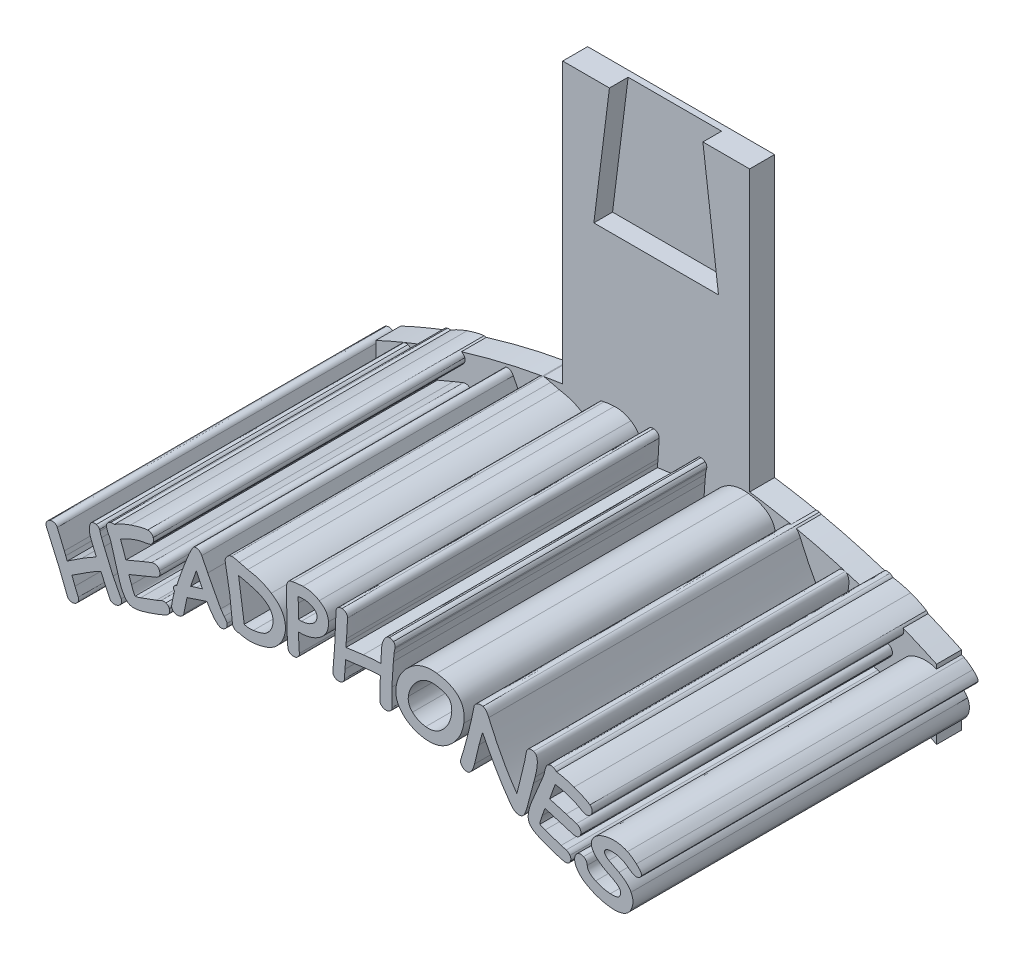
SolidWorks part; units mm, degrees
ref_plane "Front Plane" through (0, 0, 0) normal (0, 0, 1) x (1, 0, 0)
ref_plane "Top Plane" through (0, 0, 0) normal (0, 1, 0) x (1, 0, 0)
ref_plane "Right Plane" through (0, 0, 0) normal (1, 0, 0) x (0, 0, -1)
sketch "Sketch1" plane through (0, 0, 0) normal (0, 0, 1) x (1, 0, 0)
  line L1 (45, 21.1673) -> (-7.9986, 21.1673) construction
  line L2 (0, 0) -> (0, 11.1673)
  line L3 (90, 0) -> (90, 11.1673)
  arc A0 (90, 11.1673) -> (0, 11.1673) centre (45, -85.0827) ccw
  arc A1 (0, 0) -> (90, 0) centre (45, -85.0827) cw
  dimension "D1" = 90
  dimension "D2" = 10
  dimension "D3" = 10
extrude "Boss-Extrude1" add sketch "Sketch1" along normal blind 4
sketch "Sketch9" plane through (0, 0, 4) normal (0, 0, 1) x (1, 0, 0)
  line L0 (45, 8.1673) -> (-22.3317, 8.1673) construction
  arc A0 (0, -3) -> (90, -3) centre (45, -88.0827) cw
  arc A1 (90, 0) -> (0, 0) centre (45, -85.0827) ccw construction
  point P11 (45, 11.1673)
  dimension "D2" = 3
  dimension "D1" = 3
sketch "Sketch2" plane through (0, 0, 4) normal (0, 0, 1) x (1, 0, 0)
  text T0 "HEADPHONES" font "Comic Sans MS" height 10
extrude "Boss-Extrude2" add sketch "Sketch2" along normal blind 50 and the other way up to surface (4 mm away) other way up to face at (45, 10.8755, 0)
sketch "Sketch11" plane through (0, 0, 0) normal (0, 0, -1) x (-1, 0, 0)
  line L1 (-60, 65) -> (-30, 65)
  line L2 (-60, 65) -> (-60, 15)
  line L3 (-60, 15) -> (-30, 15)
  line L4 (-30, 65) -> (-30, 15)
  dimension "D1" = 30
  dimension "D2" = 30
  dimension "D3" = 50
  dimension "D4" = 15
extrude "Boss-Extrude3" add sketch "Sketch11" against normal up to surface (4 mm away) up to face at (33.925, 15.7329, 4)
sketch "Sketch14" plane through (0, 0, 4) normal (0, 0, 1) x (1, 0, 0)
  line L0 (37.5, 65) -> (35, 45)
  line L1 (60, 65) -> (30, 65) construction
  line L2 (35, 45) -> (55, 45)
  line L3 (55, 45) -> (52.5, 65)
  line L4 (52.5, 65) -> (37.5, 65)
  line L5 (30, 65) -> (30, 20.1032) construction
  dimension "D1" = 20
  dimension "D2" = 20
  dimension "D3" = 15
  dimension "D4" = 7.5
  dimension "D5" = 5
extrude "Cut-Extrude2" cut sketch "Sketch14" against normal offset from surface (3 mm away) 1 up to face at (46.1979, 10.5073, 0)
